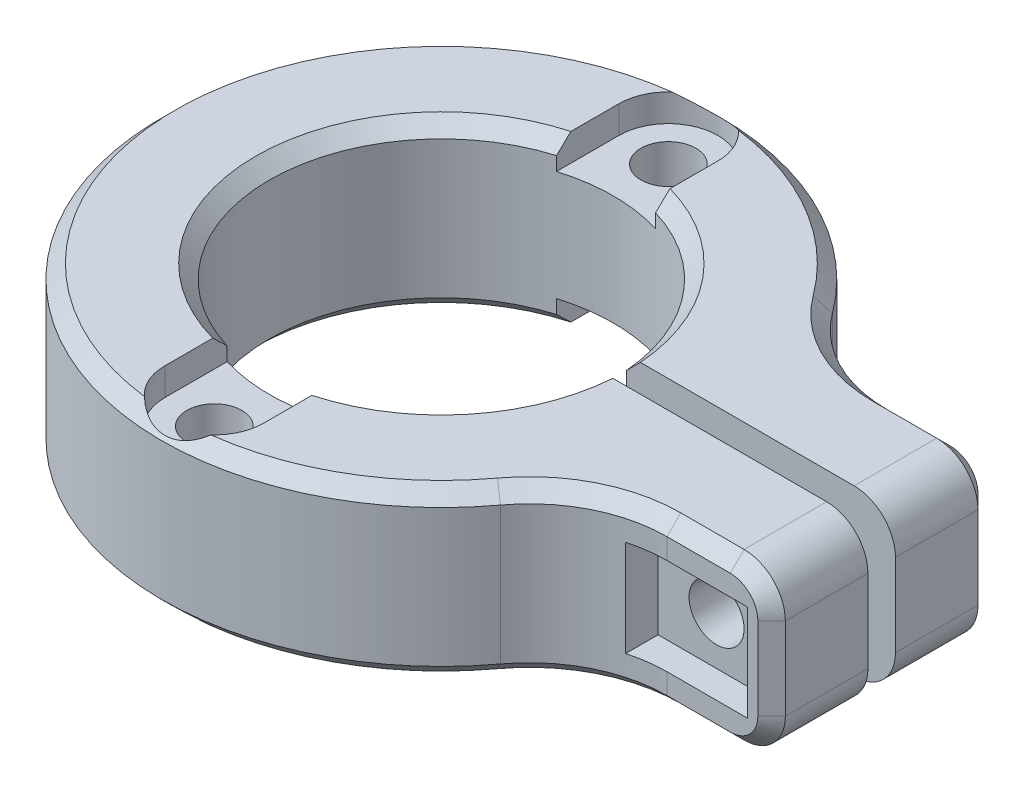
SolidWorks part; units mm, degrees
ref_plane "Front Plane" through (0, 0, 0) normal (0, 0, 1) x (1, 0, 0)
ref_plane "Top Plane" through (0, 0, 0) normal (0, 1, 0) x (1, 0, 0)
ref_plane "Right Plane" through (0, 0, 0) normal (1, 0, 0) x (0, 0, -1)
sketch "Sketch1" plane through (0, 0, 0) normal (0, 1, 0) x (1, 0, 0)
  line L0 (0, 0) -> (41.1861, 0) construction
  line L5 (12.4599, -1) -> (32, -1)
  line L8 (18.681, -8) -> (32, -8)
  line L9 (32, 8) -> (32, -8)
  line L10 (12.4599, 1) -> (32, 1)
  line L11 (25.2679, 1) -> (25.2679, -1) construction
  line L12 (18.681, 8) -> (32, 8)
  circle A0 centre (0, 0) radius 20.3219
  circle A1 centre (0, 0) radius 12.5
  circle A2 centre (0, 0) radius 16.5 construction
  circle A3 centre (0, 16.5) radius 2
  circle A4 centre (0, -16.5) radius 2
  point P11 (32, 0)
  point P23 (25.2679, 0)
  dimension "D1" = 25
  dimension "D2" = 4
  dimension "D3" = 16
  dimension "D4" = 32
  dimension "D5" = 2
extrude "Boss-Extrude1" add sketch "Sketch1" along normal mid plane 12 contours A1 L10 A0 L5 A4 A3 | A0 L10 L9 L12 | A0 L8 L9 L5 region at (16.3786, 0, 1.5746) region at (25.8451, 0, 4.5762) region at (25.8451, 0, -4.5762)
sketch "Sketch2" plane through (0, 0, 8) normal (0, 0, 1) x (1, 0, 0)
  line L0 (32, 0) -> (18.681, 0) construction
  line L1 (32, 6) -> (32, -6) construction
  line L2 (18.681, 6) -> (18.681, -6) construction
  line L3 (26, 3.5) -> (26, -3.5) construction
  line L4 (21.75, 3.5) -> (30.25, 3.5)
  line L5 (21.75, 3.5) -> (21.75, -3.5)
  line L6 (21.75, -3.5) -> (30.25, -3.5)
  line L7 (30.25, 3.5) -> (30.25, -3.5)
  point P10 (21.75, 0)
  dimension "D1" = 7
  dimension "D2" = 8.5
  dimension "D3" = 26
extrude "Cut-Extrude1" cut sketch "Sketch2" against normal blind 2
hole_wizard "Hole1" positions "Sketch3" profile "Sketch4" legacy
sketch "Sketch3" plane through (0, 0, -8) normal (0, 0, -1) x (-1, 0, 0)
  line L0 (-26, 3.5) -> (-26, -3.5) construction
  point P0 (-26, 0)
sketch "Sketch4" plane through (26, 0, -8) normal (1, 0, 0) x (0, 1, 0)
  line L0 (0, 0) -> (0, 13.999)
  line L1 (0, 13.999) -> (2, 13.999)
  line L2 (2, 13.999) -> (2, 2)
  line L3 (2, 2) -> (3.75, 2)
  line L4 (3.75, 2) -> (3.75, 0)
  line L5 (3.75, 0) -> (0, 0)
  line L6 (0, 110) -> (0, -10) construction
  dimension "Diameter" = 4
  dimension "Depth" = 13.999
  dimension "C-Bore Diameter" = 7.5
  dimension "C-Bore Depth" = 2
fillet "Fillet1" radius 10 2 edges at (18.681, 0, -8) (18.681, 0, 8)
fillet "Fillet2" radius 3 4 edges at (32, -6, -4.5) (32, -6, 4.5) (32, 6, 4.5) (32, 6, -4.5)
sketch "Sketch5" plane through (0, 6, 0) normal (0, 1, 0) x (1, 0, 0)
  line L0 (-3.6, 16.5) -> (-3.6, -16.5)
  line L1 (3.6, 16.5) -> (3.6, -16.5)
  circle A0 centre (0, 16.5) radius 3.6
  circle A1 centre (0, -16.5) radius 3.6
  circle M3 centre (0, -16.5) radius 2
  circle M4 centre (0, 16.5) radius 2
  arc M8 (12.4599, -1) -> (12.4599, 1) centre (0, 0) cw
  dimension "D1" = 7.2
extrude "Cut-Extrude2" cut sketch "Sketch5" against normal blind 2 contours A1 M3 | A1 L1 L0 M8 | L1 L0 M8 | A0 L0 L1 M8 | A0 M4 | M4 | M3 region at (0, 6, -12.8149) region at (0, 6, -19.9982) region at (0, 6, 0) region at (0, 6, 12.5851) region at (0, 6, 13.0018) region at (0, 6, 16.5) region at (0, 6, -16.5)
mirror "Mirror1" about plane through (0, 0, 0) normal (0, 1, 0) of "Cut-Extrude2"
chamfer "Chamfer1" distance 1 angle 45 22 edges at (-20.3219, -6, 0) (19.8936, -6, -9.0736) (19.8936, -6, 9.0736) (26.7006, -6, -8) (26.7006, -6, 8) (31.1213, -5.1213, -8) (31.1213, -5.1213, 8) (32, 0, -8) (32, 0, 8) (31.1213, 5.1213, -8) (31.1213, 5.1213, 8) (26.7006, 6, -8) (26.7006, 6, 8) (19.8936, 6, -9.0736) (19.8936, 6, 9.0736) (-20.3219, 6, 0) (9.7246, -6, 7.8538) (9.7246, -6, -7.8538) (-12.5, -6, 0) (9.7246, 6, 7.8538) (-12.5, 6, 0) (9.7246, 6, -7.8538)
